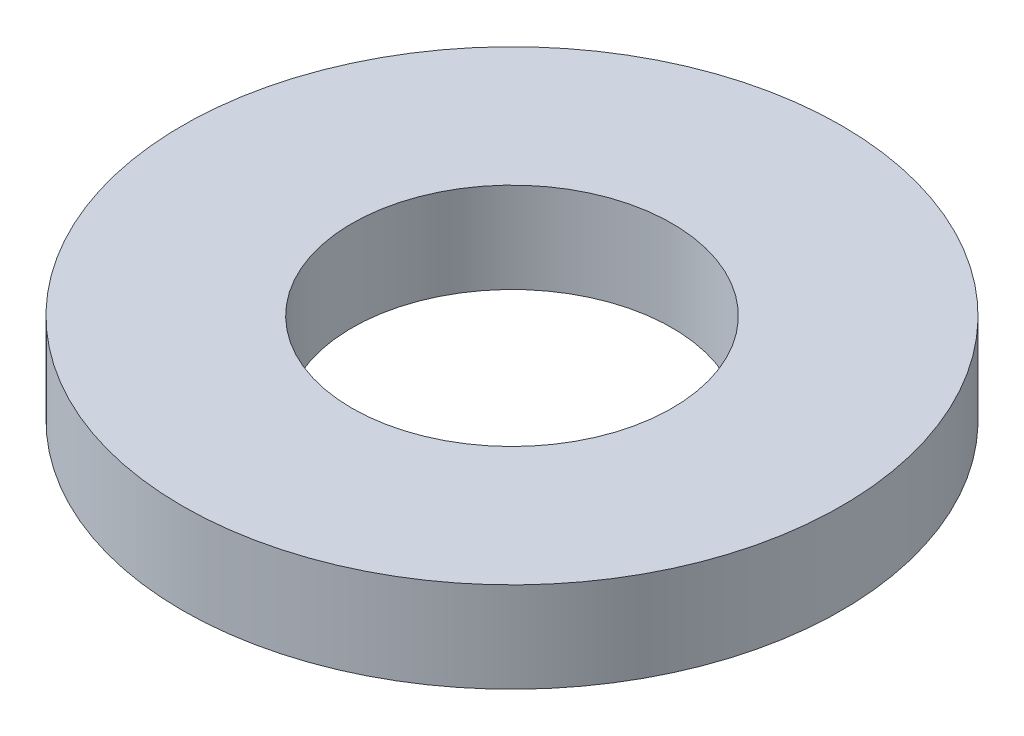
SolidWorks part; units mm, degrees
ref_plane "Front Plane" through (0, 0, 0) normal (0, 0, 1) x (1, 0, 0)
ref_plane "Top Plane" through (0, 0, 0) normal (0, 1, 0) x (1, 0, 0)
ref_plane "Right Plane" through (0, 0, 0) normal (1, 0, 0) x (0, 0, -1)
sketch "Sketch1" plane through (0, 0, 0) normal (0, 1, 0) x (1, 0, 0)
  circle A0 centre (0, 0) radius 87.5
  dimension "FLANGE_OD" = 175
extrude "Boss-Extrude1" add sketch "Sketch1" along normal blind 24
sketch "Sketch2" plane through (0, 0, 0) normal (0, 1, 0) x (1, 0, 0)
  circle A0 centre (0, 0) radius 42.5
  dimension "BORE_D" = 85
extrude "Cut-Extrude1" cut sketch "Sketch2" along normal through all
sketch "Sketch3" plane through (0, 24, 0) normal (0, 1, 0) x (1, 0, 0)
  circle A0 centre (0, 0) radius 29.9731 construction
  circle A1 centre (-29.9731, 0) radius 4.7308
  dimension "BOLT_D" = 9.4616
  dimension "BOLT_PCD" = 59.9462
extrude "Cut-Extrude2" cut sketch "Sketch3" against normal blind 16.8696 rebuild error yes
pattern_circular "CirPattern1" count 4 over 360 rebuild error yes
